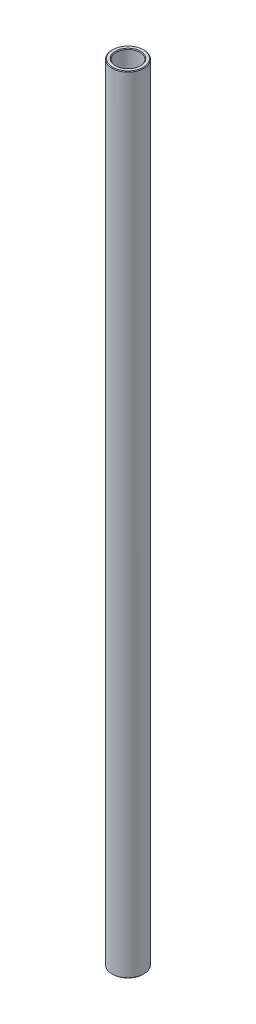
SolidWorks part; units mm, degrees
ref_plane "Front Plane" through (0, 0, 0) normal (0, 0, 1) x (1, 0, 0)
ref_plane "Top Plane" through (0, 0, 0) normal (0, 1, 0) x (1, 0, 0)
ref_plane "Right Plane" through (0, 0, 0) normal (1, 0, 0) x (0, 0, -1)
sketch "Sketch1" plane through (0, 0, 0) normal (0, 0, 1) x (1, 0, 0)
  line L0 (0, 11.6086) -> (0, -11.6086) construction
  line L1 (4.7625, 156.7656) -> (6.35, 156.7656)
  line L2 (6.35, 156.7656) -> (6.35, -156.7656)
  line L3 (6.35, -156.7656) -> (4.7625, -156.7656)
  line L4 (4.7625, -156.7656) -> (4.7625, 156.7656)
  line L5 (4.7625, 0) -> (0, 0) construction
  dimension "D1" = 9.525
  dimension "D2" = 12.7
  dimension "D3" = 313.5312
revolve "Revolve1" add sketch "Sketch1" angle 360 about L0
chamfer "Chamfer1" distance 0.254 angle 45 4 edges at (-4.7625, -156.7656, 0) (-6.35, -156.7656, 0) (-6.35, 156.7656, 0) (-4.7625, 156.7656, 0)
